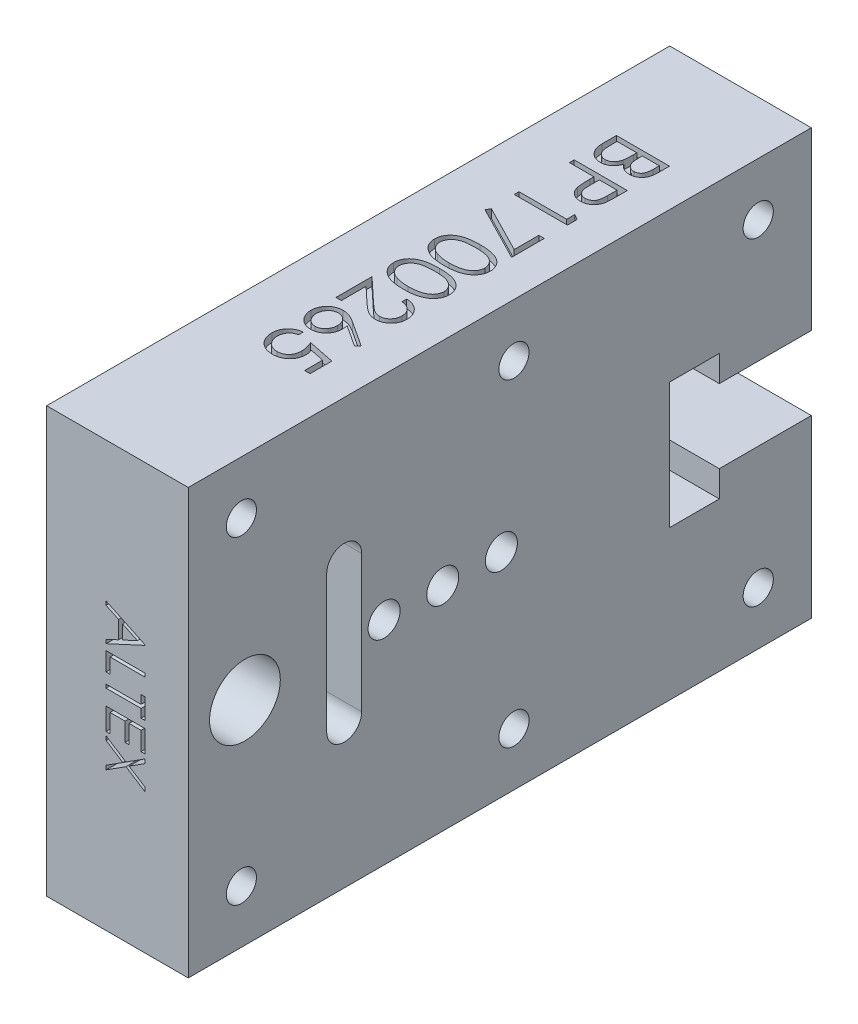
SolidWorks part; units mm, degrees
ref_plane "Front Plane" through (0, 0, 0) normal (1, 0, 0) x (0, 1, 0)
ref_plane "Top Plane" through (0, 0, 0) normal (0, 0, 1) x (0, 1, 0)
ref_plane "Right Plane" through (0, 0, 0) normal (0, 1, 0) x (-1, 0, 0)
sketch "Sketch1" plane through (0, 0, 0) normal (1, 0, 0) x (0, 1, 0)
  line L1 (-19.05, -25.4) -> (19.05, -25.4)
  line L2 (-19.05, -25.4) -> (-19.05, 25.4)
  line L3 (-19.05, 25.4) -> (19.05, 25.4)
  line L4 (19.05, -25.4) -> (19.05, 25.4)
  line L5 (-19.05, -25.4) -> (19.05, 25.4) construction
  line L6 (-19.05, 25.4) -> (19.05, -25.4) construction
  point P0 (0, 0)
  dimension "D1" = 38.1
  dimension "D2" = 50.8
extrude "Boss-Extrude1" add sketch "Sketch1" along normal blind 12.7
sketch "Sketch2" plane through (12.7, 0, 0) normal (1, 0, 0) x (0, 1, 0)
  line L0 (0, -25.4) -> (0, -12.7) construction
  line L1 (-19.05, -25.4) -> (19.05, -25.4) construction
  line L2 (3.302, -17.145) -> (5.6515, -17.145)
  line L3 (-5.6515, -12.7) -> (5.6515, -12.7)
  line L4 (-5.6515, -12.7) -> (-5.6515, -17.145)
  line L5 (-5.6515, -17.145) -> (-3.302, -17.145)
  line L6 (5.6515, -12.7) -> (5.6515, -17.145)
  line L8 (-3.302, -17.145) -> (-3.302, -25.4)
  line L9 (-3.302, -25.4) -> (3.302, -25.4)
  line L10 (3.302, -17.145) -> (3.302, -25.4)
  dimension "D1" = 12.7
  dimension "D2" = 6.604
  dimension "D3" = 3.302
  dimension "D4" = 4.445
  dimension "D5" = 5.6515
  dimension "D6" = 11.303
extrude "Cut-Extrude1" cut sketch "Sketch2" against normal up to vertex (12.7 mm away)
sketch "Sketch3" plane through (0, 0, 0) normal (-1, 0, 0) x (0, -1, 0)
  line L0 (-3.13, 14.645) -> (3.13, 14.645) construction
  line L1 (-0.4826, 14.391) -> (0.4826, 14.391) construction
  line L2 (-0.4826, 14.391) -> (-0.4826, 11.4446) construction
  line L3 (-0.4826, 11.4446) -> (0.4826, 11.4446) construction
  line L4 (0.4826, 14.391) -> (0.4826, 11.4446) construction
  line L5 (-0.4826, 14.391) -> (0.4826, 11.4446) construction
  line L6 (-0.4826, 11.4446) -> (0.4826, 14.391) construction
  line L7 (0, 14.645) -> (0, 10.007) construction
  line L8 (-1.2934, 9.385) -> (6.2665, 9.385) construction
  line L9 (-0.4826, 6.1846) -> (0.4826, 6.1846) construction
  line L10 (-0.4826, 6.1846) -> (-0.4826, 9.131) construction
  line L11 (-0.4826, 9.131) -> (0.4826, 9.131) construction
  line L12 (0.4826, 6.1846) -> (0.4826, 9.131) construction
  line L13 (-0.4826, 6.1846) -> (0.4826, 9.131) construction
  line L14 (-0.4826, 9.131) -> (0.4826, 6.1846) construction
  line L15 (-8.31, 9.385) -> (-4.39, 9.385) construction
  line L16 (0, 10.007) -> (0, -0.5586) construction
  line L17 (-1.5588, 4.125) -> (6.2665, 4.125) construction
  line L18 (-0.4826, 0.9246) -> (0.4826, 0.9246) construction
  line L19 (-0.4826, 0.9246) -> (-0.4826, 3.871) construction
  line L20 (-0.4826, 3.871) -> (0.4826, 3.871) construction
  line L21 (0.4826, 0.9246) -> (0.4826, 3.871) construction
  line L22 (-0.4826, 0.9246) -> (0.4826, 3.871) construction
  line L23 (-0.4826, 3.871) -> (0.4826, 0.9246) construction
  line L24 (-8.31, 4.125) -> (-4.39, 4.125) construction
  circle A0 centre (0, 12.9178) radius 1.4351
  circle A1 centre (0, 7.6578) radius 1.4351
  circle A2 centre (0, 2.3978) radius 1.4351
  dimension "D1" = 2.8702
  dimension "D2" = 2.8702
  dimension "D10" = 2.8702
  dimension "D3" = 2.9464
  dimension "D4" = 0.9652
  dimension "D5" = 0.254
  dimension "D6" = 2.9464
  dimension "D7" = 0.254
  dimension "D8" = 2.9464
  dimension "D9" = 0.254
extrude "Cut-Extrude2" cut sketch "Sketch3" against normal up to vertex (12.7 mm away)
sketch "Sketch6" plane through (0, 0, 25.4) normal (0, 0, 1) x (1, 0, 0)
  line L0 (7.7518, 12.7) -> (7.7518, -12.7) construction
  text T0 "ALTEX" font "Comic Sans MS" height in points 16
extrude "Cut-Extrude4" cut sketch "Sketch6" against normal blind 0.762
sketch "Sketch7" plane through (0, -19.05, 0) normal (0, -1, 0) x (1, 0, 0)
  line L0 (6.35, 25.4) -> (6.35, -25.4) construction
  line L1 (12.7, -25.4) -> (0, -25.4) construction
  line L2 (12.7, 25.4) -> (0, 25.4) construction
  text T0 "TU-101" font "Century Gothic" height in points 18
extrude "Cut-Extrude5" cut sketch "Sketch7" against normal blind 0.762
sketch "Sketch8" plane through (0, 19.05, 0) normal (0, 1, 0) x (-1, 0, 0)
  line L0 (-4.5604, -25.4) -> (-4.5604, 25.4) construction
  line L1 (-12.7, -25.4) -> (0, -25.4) construction
  line L2 (-12.7, 25.4) -> (0, 25.4) construction
  text T0 "BP1700265" font "Century Gothic" height in points 18
extrude "Cut-Extrude6" cut sketch "Sketch8" against normal blind 0.762
sketch "Sketch9" plane through (0, 0, 25.4) normal (0, 0, 1) x (1, 0, 0)
  line L0 (1.2659, 19.05) -> (1.2659, -19.05) construction
  line L1 (12.7, 19.05) -> (0, 19.05) construction
  line L2 (12.7, -19.05) -> (0, -19.05) construction
  text T0 "PCHI#10" font "Comic Sans MS" height in points 14
sketch "Sketch10" plane through (12.7, 0, 0) normal (1, 0, 0) x (0, 1, 0)
  line L0 (-19.05, 25.4) -> (-19.05, -25.4) construction
  line L1 (-13.716, 17.6775) -> (-10.922, 19.2907)
  line L2 (-10.922, 19.2907) -> (-10.922, 22.5169)
  line L3 (-10.922, 22.5169) -> (-13.716, 24.13)
  line L4 (-13.716, 24.13) -> (-16.51, 22.5169)
  line L5 (-16.51, 22.5169) -> (-16.51, 19.2907)
  line L6 (-16.51, 19.2907) -> (-13.716, 17.6775)
  line L7 (13.716, 17.6775) -> (16.51, 19.2907)
  line L8 (16.51, 19.2907) -> (16.51, 22.5169)
  line L9 (16.51, 22.5169) -> (13.716, 24.13)
  line L10 (13.716, 24.13) -> (10.922, 22.5169)
  line L11 (10.922, 22.5169) -> (10.922, 19.2907)
  line L12 (10.922, 19.2907) -> (13.716, 17.6775)
  line L13 (19.05, -25.4) -> (19.05, 25.4) construction
  line L14 (19.05, 25.4) -> (-19.05, 25.4) construction
  line L15 (-19.05, -25.4) -> (-3.302, -25.4) construction
  line L16 (-11.3275, -9.398) -> (-12.9407, -6.604)
  line L17 (-12.9407, -6.604) -> (-16.1669, -6.604)
  line L18 (-16.1669, -6.604) -> (-17.78, -9.398)
  line L19 (-17.78, -9.398) -> (-16.1669, -12.192)
  line L20 (-16.1669, -12.192) -> (-12.9407, -12.192)
  line L21 (-12.9407, -12.192) -> (-11.3275, -9.398)
  line L22 (17.78, -9.398) -> (16.1669, -6.604)
  line L23 (16.1669, -6.604) -> (12.9407, -6.604)
  line L24 (12.9407, -6.604) -> (11.3275, -9.398)
  line L25 (11.3275, -9.398) -> (12.9407, -12.192)
  line L26 (12.9407, -12.192) -> (16.1669, -12.192)
  line L27 (16.1669, -12.192) -> (17.78, -9.398)
  circle A0 centre (-13.716, 20.9038) radius 2.794 construction
  circle A1 centre (13.716, 20.9038) radius 2.794 construction
  circle A2 centre (-14.5538, -9.398) radius 2.794 construction
  circle A3 centre (14.5538, -9.398) radius 2.794 construction
  dimension "D1" = 5.588
  dimension "D2" = 5.588
  dimension "D3" = 2.54
  dimension "D4" = 2.54
  dimension "D5" = 1.27
  dimension "D6" = 1.27
  dimension "D7" = 5.588
  dimension "D8" = 5.588
  dimension "D9" = 1.27
  dimension "D10" = 1.27
  dimension "D11" = 13.208
extrude "Cut-Extrude8" cut sketch "Sketch10" against normal blind 2.54
sketch "Sketch11" plane through (0, 0, 0) normal (-1, 0, 0) x (0, -1, 0)
  line L0 (-13.716, 24.13) -> (-13.716, 17.6775) construction
  line L1 (-13.716, 17.6775) -> (13.716, 24.13) construction
  line L2 (13.716, 24.13) -> (13.716, 17.6775) construction
  line L3 (13.716, 17.6775) -> (11.3275, -9.398) construction
  line L4 (11.3275, -9.398) -> (17.78, -9.398) construction
  line L5 (17.78, -9.398) -> (-16.1669, -6.604) construction
  line L6 (-16.1669, -6.604) -> (-12.9407, -12.192) construction
  line L8 (-13.716, 24.13) -> (-16.51, 22.5169)
  line L9 (-16.51, 22.5169) -> (-16.51, 19.2907)
  line L10 (-16.51, 19.2907) -> (-13.716, 17.6775)
  line L11 (-13.716, 17.6775) -> (-10.922, 19.2907)
  line L12 (-10.922, 19.2907) -> (-10.922, 22.5169)
  line L13 (-10.922, 22.5169) -> (-13.716, 24.13)
  line L14 (13.716, 17.6775) -> (16.51, 19.2907)
  line L15 (16.51, 19.2907) -> (16.51, 22.5169)
  line L16 (16.51, 22.5169) -> (13.716, 24.13)
  line L17 (13.716, 24.13) -> (10.922, 22.5169)
  line L18 (10.922, 22.5169) -> (10.922, 19.2907)
  line L19 (10.922, 19.2907) -> (13.716, 17.6775)
  line L20 (17.78, -9.398) -> (16.1669, -6.604)
  line L21 (16.1669, -6.604) -> (12.9407, -6.604)
  line L22 (12.9407, -6.604) -> (11.3275, -9.398)
  line L23 (11.3275, -9.398) -> (12.9407, -12.192)
  line L24 (12.9407, -12.192) -> (16.1669, -12.192)
  line L25 (16.1669, -12.192) -> (17.78, -9.398)
  line L26 (-16.1669, -6.604) -> (-17.78, -9.398)
  line L27 (-17.78, -9.398) -> (-16.1669, -12.192)
  line L28 (-16.1669, -12.192) -> (-12.9407, -12.192)
  line L29 (-12.9407, -12.192) -> (-11.3275, -9.398)
  line L30 (-11.3275, -9.398) -> (-12.9407, -6.604)
  line L31 (-12.9407, -6.604) -> (-16.1669, -6.604)
  circle A0 centre (-14.5538, -9.398) radius 1.651 construction
  circle A1 centre (14.5538, -9.398) radius 1.651 construction
  circle A2 centre (13.716, 20.9038) radius 1.651 construction
  circle A3 centre (-13.716, 20.9038) radius 1.7145 construction
  circle A4 centre (-13.716, 20.9038) radius 2.794 construction
  circle A5 centre (13.716, 20.9038) radius 2.794 construction
  circle A6 centre (14.5538, -9.398) radius 2.794 construction
  circle A7 centre (-14.5538, -9.398) radius 2.794 construction
  dimension "D1" = 3.429
  dimension "D2" = 3.302
extrude "Cut-Extrude9" cut sketch "Sketch11" against normal blind 2.54
sketch "Sketch12" plane through (2.54, 0, 0) normal (-1, 0, 0) x (0, -1, 0)
  line L0 (-13.716, 17.6775) -> (-13.716, 24.13) construction
  line L1 (-13.716, 24.13) -> (13.716, 24.13) construction
  line L2 (13.716, 24.13) -> (13.716, 17.6775) construction
  line L3 (13.716, 17.6775) -> (16.1669, -6.604) construction
  line L4 (16.1669, -6.604) -> (12.9407, -12.192) construction
  line L5 (12.9407, -12.192) -> (-12.9407, -12.192) construction
  line L6 (-12.9407, -12.192) -> (-16.1669, -6.604) construction
  circle A0 centre (-14.5538, -9.398) radius 1.7145
  circle A1 centre (14.5538, -9.398) radius 1.7145
  circle A2 centre (13.716, 20.9038) radius 1.7145
  circle A3 centre (-13.716, 20.9038) radius 1.7145
  dimension "D1" = 3.429
extrude "Cut-Extrude10" cut sketch "Sketch12" against normal up to vertex
sketch "Sketch17" plane through (12.7, 0, 0) normal (1, 0, 0) x (0, 1, 0)
  line L12 (-3.2258, -25.4762) -> (-3.2258, -17.0688)
  line L13 (-3.2258, -25.4762) -> (-3.2258, -17.0688)
  line L14 (-3.2258, -17.0688) -> (-5.5753, -17.0688)
  line L15 (-3.2258, -17.0688) -> (-5.5753, -17.0688)
  line L16 (-5.5753, -17.0688) -> (-5.5753, -12.7762)
  line L17 (-5.5753, -17.0688) -> (-5.5753, -12.7762)
  line L24 (-5.5753, -12.7762) -> (5.5753, -12.7762)
  line L25 (-5.5753, -12.7762) -> (5.5753, -12.7762)
  line L26 (-3.2258, -25.4762) -> (-3.2258, -17.0688)
  line L27 (-3.2258, -25.4762) -> (-3.2258, -17.0688)
  line L28 (-3.2258, -17.0688) -> (-5.5753, -17.0688)
  line L29 (-3.2258, -17.0688) -> (-5.5753, -17.0688)
  line L34 (5.5753, -12.7762) -> (5.5753, -17.0688)
  line L35 (5.5753, -12.7762) -> (5.5753, -17.0688)
  line L36 (5.5753, -17.0688) -> (3.2258, -17.0688)
  line L37 (5.5753, -17.0688) -> (3.2258, -17.0688)
  line L38 (3.2258, -17.0688) -> (3.2258, -25.4762)
  line L39 (3.2258, -17.0688) -> (3.2258, -25.4762)
  line L40 (3.2258, -25.4762) -> (19.1262, -25.4762)
  line L41 (3.2258, -25.4762) -> (19.1262, -25.4762)
  line L42 (19.1262, -25.4762) -> (19.1262, 25.4762)
  line L43 (19.1262, -25.4762) -> (19.1262, 25.4762)
  line L44 (19.1262, 25.4762) -> (-19.1262, 25.4762)
  line L45 (19.1262, 25.4762) -> (-19.1262, 25.4762)
  line L46 (-19.1262, 25.4762) -> (-19.1262, -25.4762)
  line L47 (-19.1262, 25.4762) -> (-19.1262, -25.4762)
  line L48 (-19.1262, -25.4762) -> (-3.2258, -25.4762)
  line L49 (-19.1262, -25.4762) -> (-3.2258, -25.4762)
  line L50 (-5.5753, -17.0688) -> (-5.5753, -12.7762)
  line L51 (-5.5753, -17.0688) -> (-5.5753, -12.7762)
  line L52 (-5.5753, -12.7762) -> (5.5753, -12.7762)
  line L53 (-5.5753, -12.7762) -> (5.5753, -12.7762)
  line L54 (5.5753, -12.7762) -> (5.5753, -17.0688)
  line L55 (5.5753, -12.7762) -> (5.5753, -17.0688)
  line L56 (5.5753, -17.0688) -> (3.2258, -17.0688)
  line L57 (5.5753, -17.0688) -> (3.2258, -17.0688)
  line L58 (3.2258, -17.0688) -> (3.2258, -25.4762)
  line L59 (3.2258, -17.0688) -> (3.2258, -25.4762)
  line L60 (3.2258, -25.4762) -> (19.1262, -25.4762)
  line L61 (3.2258, -25.4762) -> (19.1262, -25.4762)
  line L62 (19.1262, -25.4762) -> (19.1262, 25.4762)
  line L63 (19.1262, -25.4762) -> (19.1262, 25.4762)
  line L64 (19.1262, 25.4762) -> (-19.1262, 25.4762)
  line L65 (19.1262, 25.4762) -> (-19.1262, 25.4762)
  line L66 (-19.1262, 25.4762) -> (-19.1262, -25.4762)
  line L67 (-19.1262, 25.4762) -> (-19.1262, -25.4762)
  line L68 (-19.1262, -25.4762) -> (-3.2258, -25.4762)
  line L69 (-19.1262, -25.4762) -> (-3.2258, -25.4762)
  dimension "D1" = 0.0762
  dimension "D2" = 0.0762
sketch "Sketch18" plane through (10.16, 0, 0) normal (1, 0, 0) x (0, 1, 0)
  line L0 (16.1669, -12.192) -> (17.78, -9.398) construction
  line L1 (17.78, -9.398) -> (16.1669, -6.604) construction
  line L2 (16.1669, -6.604) -> (12.9407, -6.604) construction
  line L3 (12.9407, -6.604) -> (11.3275, -9.398) construction
  line L4 (11.3275, -9.398) -> (12.9407, -12.192) construction
  line L5 (12.9407, -12.192) -> (16.1669, -12.192) construction
  line L6 (-16.51, 19.2907) -> (-13.716, 17.6775)
  line L7 (-13.716, 17.6775) -> (-10.922, 19.2907)
  line L8 (-10.922, 19.2907) -> (-10.922, 22.5169)
  line L9 (-10.922, 22.5169) -> (-13.716, 24.13)
  line L10 (-13.716, 24.13) -> (-16.51, 22.5169)
  line L11 (-16.51, 22.5169) -> (-16.51, 19.2907)
  line L12 (-16.51, 19.2907) -> (-13.716, 17.6775)
  line L13 (-13.716, 17.6775) -> (-10.922, 19.2907)
  line L14 (-10.922, 19.2907) -> (-10.922, 22.5169)
  line L15 (-10.922, 22.5169) -> (-13.716, 24.13)
  line L16 (-13.716, 24.13) -> (-16.51, 22.5169)
  line L17 (-16.51, 22.5169) -> (-16.51, 19.2907)
  line L18 (10.922, 19.2907) -> (13.716, 17.6775)
  line L19 (13.716, 17.6775) -> (16.51, 19.2907)
  line L20 (16.51, 19.2907) -> (16.51, 22.5169)
  line L21 (16.51, 22.5169) -> (13.716, 24.13)
  line L22 (13.716, 24.13) -> (10.922, 22.5169)
  line L23 (10.922, 22.5169) -> (10.922, 19.2907)
  line L24 (10.922, 19.2907) -> (13.716, 17.6775)
  line L25 (13.716, 17.6775) -> (16.51, 19.2907)
  line L26 (16.51, 19.2907) -> (16.51, 22.5169)
  line L27 (16.51, 22.5169) -> (13.716, 24.13)
  line L28 (13.716, 24.13) -> (10.922, 22.5169)
  line L29 (10.922, 22.5169) -> (10.922, 19.2907)
  line L30 (-12.9407, -12.192) -> (-11.3275, -9.398) construction
  line L31 (-11.3275, -9.398) -> (-12.9407, -6.604) construction
  line L32 (-12.9407, -6.604) -> (-16.1669, -6.604) construction
  line L33 (-16.1669, -6.604) -> (-17.78, -9.398) construction
  line L34 (-17.78, -9.398) -> (-16.1669, -12.192) construction
  line L35 (-16.1669, -12.192) -> (-12.9407, -12.192) construction
  line L36 (16.1669, -12.192) -> (17.78, -9.398)
  line L37 (17.78, -9.398) -> (16.1669, -6.604)
  line L38 (16.1669, -6.604) -> (12.9407, -6.604)
  line L39 (12.9407, -6.604) -> (11.3275, -9.398)
  line L40 (11.3275, -9.398) -> (12.9407, -12.192)
  line L41 (12.9407, -12.192) -> (16.1669, -12.192)
  line L42 (-12.9407, -12.192) -> (-11.3275, -9.398)
  line L43 (-11.3275, -9.398) -> (-12.9407, -6.604)
  line L44 (-12.9407, -6.604) -> (-16.1669, -6.604)
  line L45 (-16.1669, -6.604) -> (-17.78, -9.398)
  line L46 (-17.78, -9.398) -> (-16.1669, -12.192)
  line L47 (-16.1669, -12.192) -> (-12.9407, -12.192)
  circle A2 centre (-14.5538, -9.398) radius 1.7145 construction
  circle A3 centre (14.5538, -9.398) radius 1.7145 construction
  circle A4 centre (-14.5538, -9.398) radius 1.7145
  circle A5 centre (14.5538, -9.398) radius 1.7145
  circle A6 centre (13.716, 20.9038) radius 1.7145 construction
  circle A7 centre (-13.716, 20.9038) radius 1.7145 construction
  circle A8 centre (13.716, 20.9038) radius 1.7145
  circle A9 centre (-13.716, 20.9038) radius 1.7145
  dimension "D1" = 0
  dimension "D2" = 0
extrude "Boss-Extrude6" add sketch "Sketch18" along normal up to vertex (2.54 mm away)
sketch "Sketch19" plane through (2.54, 0, 0) normal (-1, 0, 0) x (0, -1, 0)
  line L0 (11.3275, -9.398) -> (12.9407, -12.192) construction
  line L1 (12.9407, -12.192) -> (16.1669, -12.192) construction
  line L2 (16.1669, -12.192) -> (17.78, -9.398) construction
  line L3 (17.78, -9.398) -> (16.1669, -6.604) construction
  line L4 (16.1669, -6.604) -> (12.9407, -6.604) construction
  line L5 (12.9407, -6.604) -> (11.3275, -9.398) construction
  line L6 (-12.9407, -6.604) -> (-16.1669, -6.604) construction
  line L7 (-16.1669, -6.604) -> (-17.78, -9.398) construction
  line L8 (-17.78, -9.398) -> (-16.1669, -12.192) construction
  line L9 (-16.1669, -12.192) -> (-12.9407, -12.192) construction
  line L10 (-12.9407, -12.192) -> (-11.3275, -9.398) construction
  line L11 (-11.3275, -9.398) -> (-12.9407, -6.604) construction
  line L12 (-10.922, 22.5169) -> (-13.716, 24.13) construction
  line L13 (-13.716, 24.13) -> (-16.51, 22.5169) construction
  line L14 (-16.51, 22.5169) -> (-16.51, 19.2907) construction
  line L15 (-16.51, 19.2907) -> (-13.716, 17.6775) construction
  line L16 (-13.716, 17.6775) -> (-10.922, 19.2907) construction
  line L17 (-10.922, 19.2907) -> (-10.922, 22.5169) construction
  line L18 (13.716, 24.13) -> (10.922, 22.5169) construction
  line L19 (10.922, 22.5169) -> (10.922, 19.2907) construction
  line L20 (10.922, 19.2907) -> (13.716, 17.6775) construction
  line L21 (13.716, 17.6775) -> (16.51, 19.2907) construction
  line L22 (16.51, 19.2907) -> (16.51, 22.5169) construction
  line L23 (16.51, 22.5169) -> (13.716, 24.13) construction
  line L24 (11.3275, -9.398) -> (12.9407, -12.192)
  line L25 (12.9407, -12.192) -> (16.1669, -12.192)
  line L26 (16.1669, -12.192) -> (17.78, -9.398)
  line L27 (17.78, -9.398) -> (16.1669, -6.604)
  line L28 (16.1669, -6.604) -> (12.9407, -6.604)
  line L29 (12.9407, -6.604) -> (11.3275, -9.398)
  line L30 (-12.9407, -6.604) -> (-16.1669, -6.604)
  line L31 (-16.1669, -6.604) -> (-17.78, -9.398)
  line L32 (-17.78, -9.398) -> (-16.1669, -12.192)
  line L33 (-16.1669, -12.192) -> (-12.9407, -12.192)
  line L34 (-12.9407, -12.192) -> (-11.3275, -9.398)
  line L35 (-11.3275, -9.398) -> (-12.9407, -6.604)
  line L36 (-10.922, 22.5169) -> (-13.716, 24.13)
  line L37 (-13.716, 24.13) -> (-16.51, 22.5169)
  line L38 (-16.51, 22.5169) -> (-16.51, 19.2907)
  line L39 (-16.51, 19.2907) -> (-13.716, 17.6775)
  line L40 (-13.716, 17.6775) -> (-10.922, 19.2907)
  line L41 (-10.922, 19.2907) -> (-10.922, 22.5169)
  line L42 (13.716, 24.13) -> (10.922, 22.5169)
  line L43 (10.922, 22.5169) -> (10.922, 19.2907)
  line L44 (10.922, 19.2907) -> (13.716, 17.6775)
  line L45 (13.716, 17.6775) -> (16.51, 19.2907)
  line L46 (16.51, 19.2907) -> (16.51, 22.5169)
  line L47 (16.51, 22.5169) -> (13.716, 24.13)
extrude "Cut-Extrude13" cut sketch "Sketch19" against normal blind 7.112
sketch "Sketch20" plane through (12.7, 0, 0) normal (1, 0, 0) x (0, 1, 0)
  line L0 (-13.716, 17.6775) -> (-13.716, -4.572) construction
  line L2 (13.716, 17.6775) -> (13.716, -6.604) construction
  line L3 (12.9407, -6.604) -> (16.1669, -6.604) construction
  line L4 (-9.0868, -6.604) -> (8.8237, -6.604) construction
  line L5 (-13.716, 1.8805) -> (-16.51, 0.2673)
  line L6 (-16.51, 0.2673) -> (-16.51, -2.9589)
  line L7 (-16.51, -2.9589) -> (-13.716, -4.572)
  line L8 (-13.716, -4.572) -> (-10.922, -2.9589)
  line L9 (-10.922, -2.9589) -> (-10.922, 0.2673)
  line L10 (-10.922, 0.2673) -> (-13.716, 1.8805)
  line L11 (13.716, 9.1931) -> (16.51, 10.8062)
  line L12 (16.51, 10.8062) -> (16.51, 14.0324)
  line L13 (16.51, 14.0324) -> (13.716, 15.6455)
  line L14 (13.716, 15.6455) -> (10.922, 14.0324)
  line L15 (10.922, 14.0324) -> (10.922, 10.8062)
  line L16 (10.922, 10.8062) -> (13.716, 9.1931)
  line L17 (-16.1669, -6.604) -> (-12.9407, -6.604) construction
  circle A0 centre (-13.716, -1.3458) radius 2.794 construction
  circle A1 centre (13.716, 12.4193) radius 2.794 construction
  dimension "D1" = 5.588
  dimension "D2" = 5.588
  dimension "D3" = 2.032
  dimension "D4" = 2.032
extrude "Cut-Extrude14" cut sketch "Sketch20" against normal blind 10.414
sketch "Sketch21" plane through (2.286, 0, 0) normal (1, 0, 0) x (0, 1, 0)
  line L0 (-16.51, 0.2673) -> (-10.922, -2.9589) construction
  line L1 (-10.922, -2.9589) -> (13.716, 9.1931) construction
  line L2 (13.716, 9.1931) -> (13.716, 15.6455) construction
  circle A0 centre (13.716, 12.4193) radius 1.651
  circle A1 centre (-13.716, -1.3458) radius 1.651
  dimension "D1" = 3.302
  dimension "D2" = 3.302
sketch "Sketch24" plane through (0, 0, 24.638) normal (0, 0, 1) x (1, 0, 0)
  line L1 (0, 19.05) -> (12.7, 19.05)
  line L2 (0, 19.05) -> (0, -19.05)
  line L3 (0, -19.05) -> (12.7, -19.05)
  line L4 (12.7, 19.05) -> (12.7, -19.05)
extrude "Boss-Extrude7" add sketch "Sketch24" along normal up to vertex (5.842 mm away)
sketch "Sketch25" plane through (0, 0, 30.48) normal (0, 0, 1) x (1, 0, 0)
  line L0 (5.3262, 19.05) -> (5.3262, -19.05) construction
  line L1 (12.7, 19.05) -> (0, 19.05) construction
  line L2 (0, -19.05) -> (12.7, -19.05) construction
  text T0 "ALTEX"
extrude "Cut-Extrude18" cut sketch "Sketch25" against normal blind 1.016
sketch "Sketch26" plane through (12.7, 0, 0) normal (1, 0, 0) x (0, 1, 0)
  line L1 (1.99, 14.975) -> (4.5632, 14.975)
  line L2 (1.99, 14.975) -> (1.99, 18.2182) construction
  line L3 (1.99, 18.2182) -> (4.5632, 18.2182)
  line L4 (4.5632, 14.975) -> (4.5632, 18.2182)
  line L5 (1.99, 14.975) -> (-4.5632, 14.975)
  line L6 (1.99, 14.975) -> (1.99, 18.2182) construction
  line L7 (1.99, 18.2182) -> (-4.5632, 18.2182)
  line L8 (-4.5632, 14.975) -> (-4.5632, 18.2182)
extrude "Cut-Extrude19" cut sketch "Sketch26" against normal up to vertex
extrude "Cut-Extrude15" cut sketch "Sketch21" against normal up to vertex (2.286 mm away)
sketch "Sketch22" plane through (12.7, 0, 0) normal (1, 0, 0) x (0, 1, 0)
  line L1 (1.99, 18.015) -> (10.71, 18.015)
  line L2 (1.99, 18.015) -> (1.99, 14.975)
  line L3 (1.99, 14.975) -> (10.71, 14.975)
  line L4 (10.71, 18.015) -> (10.71, 14.975)
sketch "Sketch23" plane through (12.7, 0, 0) normal (1, 0, 0) x (0, 1, 0)
  line L4 (-4.36, 14.975) -> (4.36, 14.975)
  line L5 (4.36, 14.975) -> (4.36, 18.015)
  line L6 (-4.36, 18.015) -> (-4.36, 14.975)
  line L7 (4.36, 18.015) -> (-4.36, 18.015)
  line L8 (4.5632, 18.2182) -> (-4.5632, 18.2182)
  line L9 (-4.5632, 18.2182) -> (-4.5632, 14.7718)
  line L10 (-4.5632, 14.7718) -> (4.5632, 14.7718)
  line L11 (4.5632, 14.7718) -> (4.5632, 18.2182)
extrude "Cut-Extrude17" cut sketch "Sketch23" against normal up to vertex (12.7 mm away)
sketch "Sketch27" plane through (2.286, 0, 0) normal (1, 0, 0) x (0, 1, 0)
  line L0 (-13.716, 1.8805) -> (-13.716, -4.572) construction
  line L2 (13.716, 9.1931) -> (13.716, 15.6455) construction
  circle A0 centre (-13.716, -1.3458) radius 1.651
  circle A1 centre (13.716, 12.4193) radius 1.651
  dimension "D1" = 3.302
  dimension "D2" = 3.302
sketch "Sketch29" plane through (12.7, 0, 0) normal (1, 0, 0) x (0, 1, 0)
  line L0 (-10.2699, 9.8318) -> (-10.2699, 11.1811) construction
  line L1 (-4.5632, 18.2182) -> (-6.1507, 18.2182) construction
  line L2 (-4.5632, 14.7718) -> (-6.9093, 14.7718) construction
  line L3 (4.5632, 18.2182) -> (6.1507, 18.2182) construction
  line L4 (4.5632, 14.7718) -> (6.9486, 14.7718) construction
  line L5 (-6.1507, 18.2182) -> (-6.1507, 14.7718) construction
  line L6 (6.1507, 18.2182) -> (6.1507, 14.7718) construction
  line L7 (-6.1507, 18.2182) -> (6.1507, 18.2182)
  line L8 (6.1507, 14.7718) -> (-6.1507, 14.7718)
  arc A0 (-6.1507, 18.2182) -> (-6.1507, 14.7718) centre (-6.1507, 16.495) ccw
  arc A1 (6.1507, 14.7718) -> (6.1507, 18.2182) centre (6.1507, 16.495) ccw
  dimension "D1" = 1.5875
  dimension "D2" = 1.5875
extrude "Cut-Extrude20" cut sketch "Sketch29" against normal up to vertex (12.7 mm away)
sketch "Sketch30" plane through (0, 0, 0) normal (-1, 0, 0) x (0, -1, 0)
  line L0 (6.1507, 14.7718) -> (-6.1507, 14.7718) construction
  line L1 (-6.1507, 18.2182) -> (6.1507, 18.2182) construction
  line L2 (6.1507, 14.7718) -> (-6.1507, 14.7718)
  line L3 (-6.1507, 18.2182) -> (6.1507, 18.2182)
  line L4 (-6.1507, 18.0658) -> (6.1507, 18.0658)
  line L5 (6.1507, 14.9242) -> (-6.1507, 14.9242)
  arc A0 (6.1507, 14.7718) -> (6.1507, 18.2182) centre (6.1507, 16.495) ccw construction
  arc A1 (-6.1507, 18.2182) -> (-6.1507, 14.7718) centre (-6.1507, 16.495) ccw construction
  arc A2 (6.1507, 14.7718) -> (6.1507, 18.2182) centre (6.1507, 16.495) ccw
  arc A3 (-6.1507, 18.2182) -> (-6.1507, 14.7718) centre (-6.1507, 16.495) ccw
  arc A4 (6.1507, 14.9242) -> (6.1507, 18.0658) centre (6.1507, 16.495) ccw
  arc A5 (-6.1507, 18.0658) -> (-6.1507, 14.9242) centre (-6.1507, 16.495) ccw
  dimension "D1" = 0.1524
extrude "Boss-Extrude8" add sketch "Sketch30" against normal up to vertex (12.7 mm away)
sketch "Sketch31" plane through (12.7, 0, 0) normal (1, 0, 0) x (0, 1, 0)
  line L6 (-10.922, 0.2673) -> (-13.716, 1.8805)
  line L7 (-13.716, 1.8805) -> (-16.51, 0.2673)
  line L8 (-16.51, 0.2673) -> (-16.51, -2.9589)
  line L9 (-16.51, -2.9589) -> (-13.716, -4.572)
  line L10 (-13.716, -4.572) -> (-10.922, -2.9589)
  line L11 (-10.922, -2.9589) -> (-10.922, 0.2673)
  line L12 (-10.922, 0.2673) -> (-13.716, 1.8805)
  line L13 (-13.716, 1.8805) -> (-16.51, 0.2673)
  line L14 (-16.51, 0.2673) -> (-16.51, -2.9589)
  line L15 (-16.51, -2.9589) -> (-13.716, -4.572)
  line L16 (-13.716, -4.572) -> (-10.922, -2.9589)
  line L17 (-10.922, -2.9589) -> (-10.922, 0.2673)
  line L18 (10.922, 10.8062) -> (13.716, 9.1931)
  line L19 (13.716, 9.1931) -> (16.51, 10.8062)
  line L20 (16.51, 10.8062) -> (16.51, 14.0324)
  line L21 (16.51, 14.0324) -> (13.716, 15.6455)
  line L22 (13.716, 15.6455) -> (10.922, 14.0324)
  line L23 (10.922, 14.0324) -> (10.922, 10.8062)
  line L24 (10.922, 10.8062) -> (13.716, 9.1931)
  line L25 (13.716, 9.1931) -> (16.51, 10.8062)
  line L26 (16.51, 10.8062) -> (16.51, 14.0324)
  line L27 (16.51, 14.0324) -> (13.716, 15.6455)
  line L28 (13.716, 15.6455) -> (10.922, 14.0324)
  line L29 (10.922, 14.0324) -> (10.922, 10.8062)
  dimension "D1" = 0
  dimension "D2" = 0
extrude "Boss-Extrude9" add sketch "Sketch31" against normal up to vertex (12.7 mm away)
sketch "Sketch35" plane through (0, 0, 0) normal (-1, 0, 0) x (0, -1, 0)
  line L0 (-11.3275, -9.398) -> (-12.9407, -6.604) construction
  line L1 (-12.9407, -6.604) -> (-16.1669, -6.604) construction
  line L2 (-16.1669, -6.604) -> (-17.78, -9.398) construction
  line L3 (-17.78, -9.398) -> (-16.1669, -12.192) construction
  line L4 (-16.1669, -12.192) -> (-12.9407, -12.192) construction
  line L5 (-12.9407, -12.192) -> (-11.3275, -9.398) construction
  line L6 (12.9407, -6.604) -> (11.3275, -9.398) construction
  line L7 (11.3275, -9.398) -> (12.9407, -12.192) construction
  line L8 (12.9407, -12.192) -> (16.1669, -12.192) construction
  line L9 (16.1669, -12.192) -> (17.78, -9.398) construction
  line L10 (17.78, -9.398) -> (16.1669, -6.604) construction
  line L11 (16.1669, -6.604) -> (12.9407, -6.604) construction
  line L12 (16.51, 22.5169) -> (13.716, 24.13) construction
  line L13 (13.716, 24.13) -> (10.922, 22.5169) construction
  line L14 (10.922, 22.5169) -> (10.922, 19.2907) construction
  line L15 (10.922, 19.2907) -> (13.716, 17.6775) construction
  line L16 (13.716, 17.6775) -> (16.51, 19.2907) construction
  line L17 (16.51, 19.2907) -> (16.51, 22.5169) construction
  line L18 (-10.922, 19.2907) -> (-10.922, 22.5169) construction
  line L19 (-10.922, 22.5169) -> (-13.716, 24.13) construction
  line L20 (-13.716, 24.13) -> (-16.51, 22.5169) construction
  line L21 (-16.51, 22.5169) -> (-16.51, 19.2907) construction
  line L22 (-16.51, 19.2907) -> (-13.716, 17.6775) construction
  line L23 (-13.716, 17.6775) -> (-10.922, 19.2907) construction
  line L24 (-11.3275, -9.398) -> (-12.9407, -6.604)
  line L25 (-12.9407, -6.604) -> (-16.1669, -6.604)
  line L26 (-16.1669, -6.604) -> (-17.78, -9.398)
  line L27 (-17.78, -9.398) -> (-16.1669, -12.192)
  line L28 (-16.1669, -12.192) -> (-12.9407, -12.192)
  line L29 (-12.9407, -12.192) -> (-11.3275, -9.398)
  line L30 (12.9407, -6.604) -> (11.3275, -9.398)
  line L31 (11.3275, -9.398) -> (12.9407, -12.192)
  line L32 (12.9407, -12.192) -> (16.1669, -12.192)
  line L33 (16.1669, -12.192) -> (17.78, -9.398)
  line L34 (17.78, -9.398) -> (16.1669, -6.604)
  line L35 (16.1669, -6.604) -> (12.9407, -6.604)
  line L36 (16.51, 22.5169) -> (13.716, 24.13)
  line L37 (13.716, 24.13) -> (10.922, 22.5169)
  line L38 (10.922, 22.5169) -> (10.922, 19.2907)
  line L39 (10.922, 19.2907) -> (13.716, 17.6775)
  line L40 (13.716, 17.6775) -> (16.51, 19.2907)
  line L41 (16.51, 19.2907) -> (16.51, 22.5169)
  line L42 (-10.922, 19.2907) -> (-10.922, 22.5169)
  line L43 (-10.922, 22.5169) -> (-13.716, 24.13)
  line L44 (-13.716, 24.13) -> (-16.51, 22.5169)
  line L45 (-16.51, 22.5169) -> (-16.51, 19.2907)
  line L46 (-16.51, 19.2907) -> (-13.716, 17.6775)
  line L47 (-13.716, 17.6775) -> (-10.922, 19.2907)
extrude "Boss-Extrude10" add sketch "Sketch35" against normal up to vertex (12.7 mm away)
hole_wizard "#6-32 Tapped Hole2" positions "Sketch37" profile "Sketch38" tap size "#6-32" standard "ANSI Inch" end condition up to next
sketch "Sketch37" plane through (0, 0, 0) normal (-1, 0, 0) x (0, -1, 0)
  line L0 (-19.05, 30.48) -> (19.05, 30.48) construction
  line L1 (-19.05, -25.4) -> (-19.05, 30.48) construction
  line L2 (19.05, 30.48) -> (19.05, -25.4) construction
  line L3 (-3.302, -25.4) -> (-19.05, -25.4) construction
  line L4 (19.05, -25.4) -> (3.302, -25.4) construction
  point P0 (-14.2875, 25.7175)
  point P2 (14.2875, 25.7175)
  point P4 (14.2875, 1.27)
  point P6 (-14.2875, 1.27)
  point P8 (-14.2875, -20.6375)
  point P10 (14.2875, -20.6375)
  point P20 (0, 0)
  point P21 (0, 0)
  point P22 (0, 0)
  dimension "D1" = 4.7625
  dimension "D2" = 4.7625
  dimension "D3" = 4.7625
  dimension "D4" = 4.7625
  dimension "D5" = 4.7625
  dimension "D6" = 4.7625
  dimension "D7" = 4.7625
  dimension "D8" = 26.67
  dimension "D9" = 26.67
sketch "Sketch38" plane through (0, 14.2875, 25.7175) normal (0, 1, 0) x (0, 0, 1)
  line L0 (0, 0) -> (0, 12.7)
  line L1 (0, 12.7) -> (1.3525, 12.7)
  line L2 (1.3525, 12.7) -> (1.3525, 0)
  line L5 (1.3525, 0) -> (0, 0)
  line L11 (0, -6.35) -> (0, 107.95) construction
  dimension "Thru Tap Drill Dia." = 2.7051
  dimension "Thru Tap Drill Depth" = 12.7
cosmetic thread "Hole Thread1" parameters "D2"=3.5052
cosmetic thread "Hole Thread2" parameters "D2"=3.5052
cosmetic thread "Hole Thread3" parameters "D2"=3.5052
cosmetic thread "Hole Thread4" parameters "D2"=3.5052
cosmetic thread "Hole Thread5" parameters "D2"=3.5052
cosmetic thread "Hole Thread6" parameters "D2"=3.5052
sketch "Sketch39" plane through (12.7, 0, 0) normal (1, 0, 0) x (0, 1, 0)
  circle A0 centre (0, 25.4) radius 3.175
  dimension "D1" = 6.35
extrude "Cut-Extrude21" cut sketch "Sketch39" against normal blind 8.128
